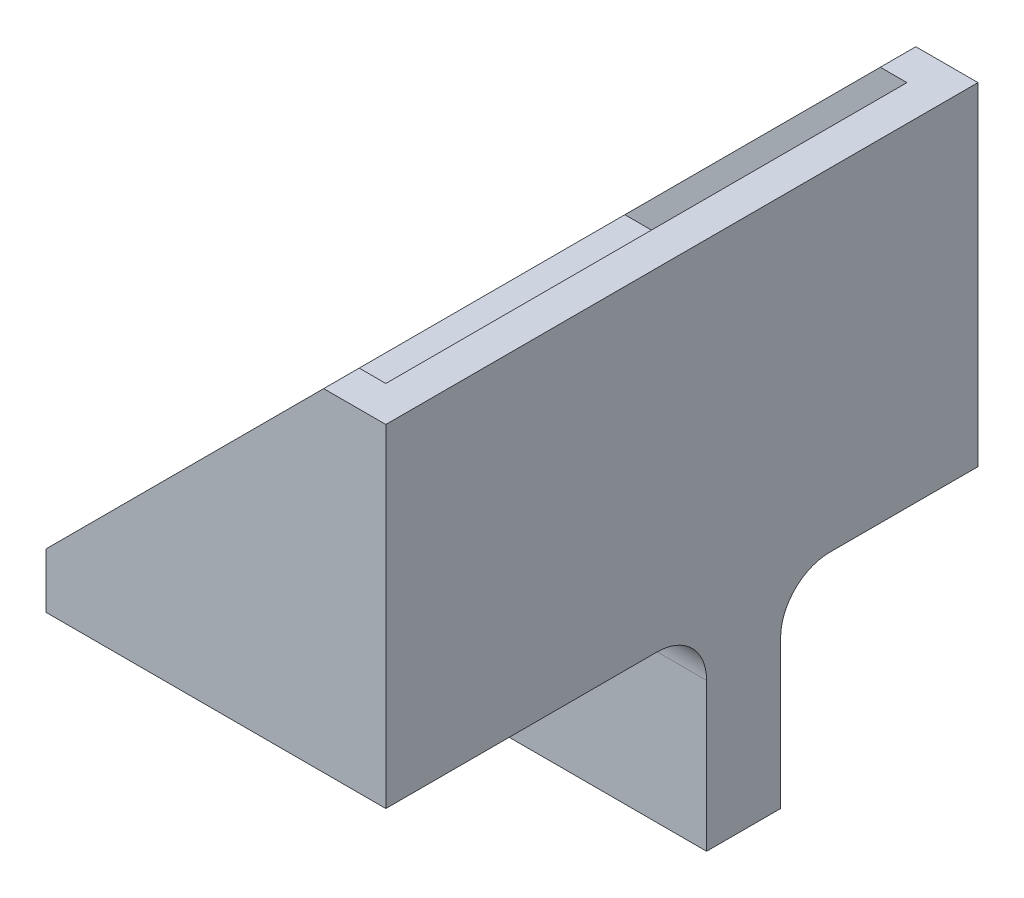
SolidWorks part; units mm, degrees
ref_plane "Front Plane" through (0, 0, 0) normal (0, 0, 1) x (1, 0, 0)
ref_plane "Top Plane" through (0, 0, 0) normal (0, 1, 0) x (1, 0, 0)
ref_plane "Right Plane" through (0, 0, 0) normal (1, 0, 0) x (0, 0, -1)
sketch "Sketch1" plane through (0, 0, 0) normal (0, 0, 1) x (1, 0, 0)
  line L0 (30.841, 29.7939) -> (-19.959, -21.0061)
  line L3 (-19.959, -21.0061) -> (30.841, -21.0061)
  line L4 (30.841, 29.7939) -> (30.841, -21.0061)
  dimension "D1" = 50.8
extrude "Boss-Extrude1" add sketch "Sketch1" along normal blind 76.2
sketch "Sketch2" plane through (0, 0, 0) normal (0, 1, 0) x (1, 0, 0)
  line L0 (-19.959, -76.2) -> (-19.959, 0) construction
  line L1 (-19.959, -4.572) -> (26.269, -4.572)
  line L2 (-19.959, -4.572) -> (-19.959, -71.628)
  line L3 (-19.959, -71.628) -> (26.269, -71.628)
  line L4 (26.269, -4.572) -> (26.269, -71.628)
  line L5 (30.841, 0) -> (-19.959, 0) construction
  line L6 (30.841, -76.2) -> (-19.959, -76.2) construction
  line L7 (30.841, -76.2) -> (30.841, 0) construction
  dimension "D1" = 4.572
  dimension "D2" = 4.572
  dimension "D3" = 4.572
extrude "Cut-Extrude1" cut sketch "Sketch2" along normal blind 32 and the other way blind 11.079
chamfer "Chamfer2" distance 8 angle 90 1 edges at (30.841, 29.7939, 38.1) first distance on face at (30.841, 4.3939, 38.1)
chamfer "Chamfer3" distance 10 angle 45 1 edges at (-19.959, -21.0061, 38.1) first distance on face at (3.9228, 2.8757, 38.1)
sketch "Sketch3" plane through (0, -11.079, 0) normal (0, 1, 0) x (1, 0, 0)
  line L2 (30.841, -25.4) -> (-12.8879, 0) construction
  line L3 (30.841, 0) -> (-12.8879, 0) construction
  line L4 (30.841, 0) -> (30.841, -25.4) construction
  line L5 (30.841, -25.4) -> (-12.8879, -25.4) construction
  line L6 (-12.8879, -76.2) -> (30.841, -76.2)
  line L7 (-12.8879, 0) -> (-12.8879, -76.2)
  line L8 (30.841, 0) -> (-12.8879, 0)
  line L9 (30.841, -76.2) -> (30.841, 0)
  line L10 (-12.8879, -76.2) -> (30.841, -76.2) construction
  line L11 (-12.8879, 0) -> (-12.8879, -76.2) construction
  line L12 (30.841, 0) -> (-12.8879, 0) construction
  line L13 (30.841, -76.2) -> (30.841, 0) construction
  line L14 (-12.8879, 0) -> (-12.8879, -25.4) construction
  circle A0 centre (8.9766, -12.7) radius 3.175
  point P5 (-12.8879, 0)
  point P9 (5.6555, -10.8618)
  dimension "D1" = 0
  dimension "D2" = 25.4
extrude "Cut-Extrude2" cut sketch "Sketch3" against normal through all contours A0
sketch "Sketch8" plane through (0, -21.0061, 0) normal (0, -1, 0) x (1, 0, 0)
  line L0 (30.841, 76.2) -> (30.841, 0) construction
  line L1 (-12.8879, 0) -> (30.841, 0) construction
  line L2 (-12.8879, 0) -> (-12.8879, 25.4) construction
  line L3 (-12.8879, 25.4) -> (30.841, 25.4) construction
  line L4 (30.841, 0) -> (30.841, 25.4) construction
  line L6 (-12.8879, 25.4) -> (30.841, 25.4)
  line L7 (-12.8879, 25.4) -> (-12.8879, 34.925)
  line L8 (-12.8879, 34.925) -> (30.841, 34.925)
  line L9 (30.841, 25.4) -> (30.841, 34.925)
  dimension "D1" = 25.4
  dimension "D2" = 9.525
extrude "Boss-Extrude3" add sketch "Sketch8" along normal blind 25.4
sketch "Sketch9" plane through (0, 0, 34.925) normal (0, 0, 1) x (1, 0, 0)
  circle A0 centre (8.9766, -33.7061) radius 3.175
  point P7 (0, 0)
  point P8 (10.2065, -36.3838)
  point P9 (0, 0)
  point P10 (7.4286, -37.5075)
  point P11 (0, 0)
  point P12 (8.9766, -33.7061)
  point P13 (8.9766, -33.7061)
  point P14 (8.9766, -33.7061)
  point P15 (8.9766, -33.7061)
  point P16 (8.9766, -33.7061)
  point P17 (8.9766, -33.7061)
  point P18 (12.6255, -31.7019)
  point P19 (12.6044, -31.5988)
  point P20 (8.9366, -33.7293)
  point P21 (16.8807, -29.115)
  point P22 (8.9532, -33.7197)
  point P23 (11.8172, -32.0561)
extrude "Cut-Extrude3" cut sketch "Sketch9" against normal through all
fillet "Fillet2" radius 6.35 2 edges at (8.9766, -21.0061, 25.4) (8.9766, -21.0061, 34.925)
